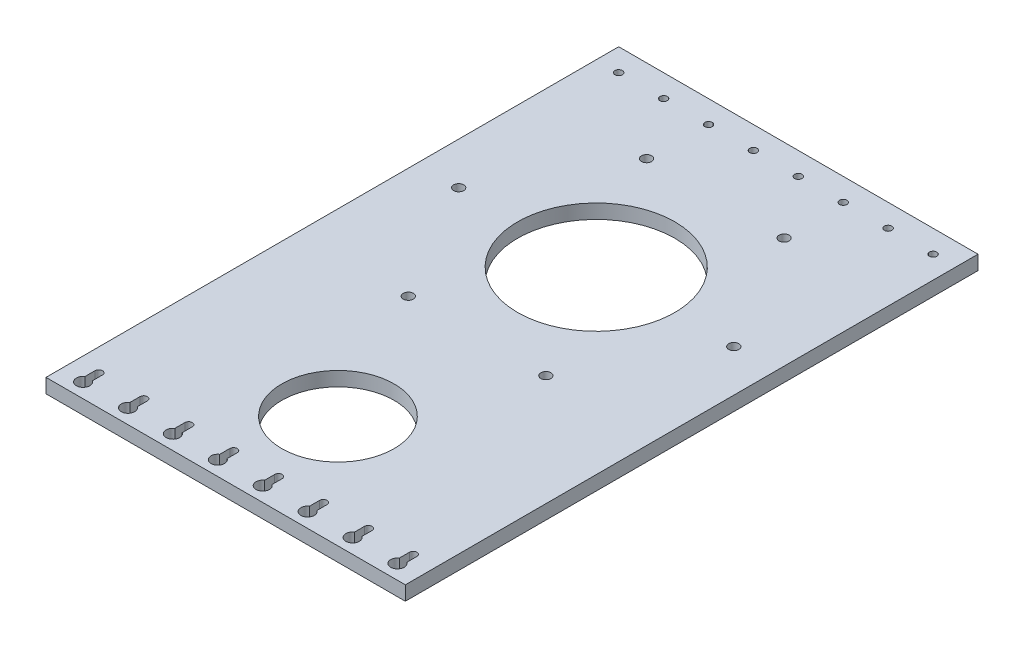
SolidWorks part; units mm, degrees
material "6061 Alloy"
ref_plane "Front Plane" through (0, 0, 0) normal (0, 0, 1) x (1, 0, 0)
ref_plane "Top Plane" through (0, 0, 0) normal (0, 1, 0) x (1, 0, 0)
ref_plane "Right Plane" through (0, 0, 0) normal (1, 0, 0) x (0, 0, -1)
sketch "Sketch1" plane through (0, 0, 0) normal (0, 1, 0) x (1, 0, 0)
  line L0 (80, 255) -> (80, 0) construction
  line L1 (0, 0) -> (160, 0)
  line L2 (0, 0) -> (0, 255)
  line L3 (0, 255) -> (160, 255)
  line L4 (160, 0) -> (160, 255)
  line L5 (80, 165) -> (141.25, 165) construction
  line L6 (10, 6.5) -> (10, 13.5) construction
  line L8 (14.5, 0) -> (14.5, 255) construction
  line L9 (14.5, 131) -> (0, 131) construction
  line L11 (0, 131) -> (0, 121) construction
  line L13 (8.35, 6.5) -> (8.35, 13.5)
  line L14 (11.65, 6.5) -> (11.65, 13.5)
  line L15 (10, 245) -> (10, 0) construction
  line L16 (31.65, 6.5) -> (31.65, 13.5)
  line L17 (28.35, 6.5) -> (28.35, 13.5)
  line L18 (30, 6.5) -> (30, 13.5) construction
  line L19 (51.65, 6.5) -> (51.65, 13.5)
  line L20 (48.35, 6.5) -> (48.35, 13.5)
  line L21 (50, 6.5) -> (50, 13.5) construction
  line L22 (71.65, 6.5) -> (71.65, 13.5)
  line L23 (68.35, 6.5) -> (68.35, 13.5)
  line L24 (70, 6.5) -> (70, 13.5) construction
  line L25 (91.65, 6.5) -> (91.65, 13.5)
  line L26 (88.35, 6.5) -> (88.35, 13.5)
  line L27 (90, 6.5) -> (90, 13.5) construction
  line L28 (111.65, 6.5) -> (111.65, 13.5)
  line L29 (108.35, 6.5) -> (108.35, 13.5)
  line L30 (110, 6.5) -> (110, 13.5) construction
  line L31 (131.65, 6.5) -> (131.65, 13.5)
  line L32 (128.35, 6.5) -> (128.35, 13.5)
  line L33 (130, 6.5) -> (130, 13.5) construction
  line L34 (151.65, 6.5) -> (151.65, 13.5)
  line L35 (148.35, 6.5) -> (148.35, 13.5)
  line L36 (150, 6.5) -> (150, 13.5) construction
  line L37 (10, 245) -> (30, 245) construction
  circle A0 centre (80, 165) radius 35
  circle A1 centre (80, 50) radius 25
  circle A2 centre (80, 165) radius 61.25 construction
  circle A3 centre (141.25, 165) radius 2.25
  circle A4 centre (110.625, 111.9559) radius 2.25
  circle A5 centre (49.375, 111.9559) radius 2.25
  circle A6 centre (18.75, 165) radius 2.25
  circle A7 centre (49.375, 218.0441) radius 2.25
  circle A8 centre (110.625, 218.0441) radius 2.25
  circle A12 centre (80, 165) radius 78 construction
  circle A13 centre (10, 245) radius 1.65
  arc A14 (8.35, 6.5) -> (11.65, 6.5) centre (10, 6.5) ccw
  arc A15 (11.65, 13.5) -> (8.35, 13.5) centre (10, 13.5) ccw
  circle A16 centre (30, 245) radius 1.65
  arc A17 (28.35, 6.5) -> (31.65, 6.5) centre (30, 6.5) ccw
  arc A18 (31.65, 13.5) -> (28.35, 13.5) centre (30, 13.5) ccw
  circle A19 centre (50, 245) radius 1.65
  arc A20 (48.35, 6.5) -> (51.65, 6.5) centre (50, 6.5) ccw
  arc A21 (51.65, 13.5) -> (48.35, 13.5) centre (50, 13.5) ccw
  circle A22 centre (70, 245) radius 1.65
  arc A23 (68.35, 6.5) -> (71.65, 6.5) centre (70, 6.5) ccw
  arc A24 (71.65, 13.5) -> (68.35, 13.5) centre (70, 13.5) ccw
  circle A25 centre (90, 245) radius 1.65
  arc A26 (88.35, 6.5) -> (91.65, 6.5) centre (90, 6.5) ccw
  arc A27 (91.65, 13.5) -> (88.35, 13.5) centre (90, 13.5) ccw
  circle A28 centre (110, 245) radius 1.65
  arc A29 (108.35, 6.5) -> (111.65, 6.5) centre (110, 6.5) ccw
  arc A30 (111.65, 13.5) -> (108.35, 13.5) centre (110, 13.5) ccw
  circle A31 centre (130, 245) radius 1.65
  arc A32 (128.35, 6.5) -> (131.65, 6.5) centre (130, 6.5) ccw
  arc A33 (131.65, 13.5) -> (128.35, 13.5) centre (130, 13.5) ccw
  circle A34 centre (150, 245) radius 1.65
  arc A35 (148.35, 6.5) -> (151.65, 6.5) centre (150, 6.5) ccw
  arc A36 (151.65, 13.5) -> (148.35, 13.5) centre (150, 13.5) ccw
  point P15 (80, 165)
  point P29 (10, 10)
  point P30 (0, 0)
  point P31 (0, 0)
  point P32 (0, 0)
  point P33 (0, 0)
  point P55 (30, 10)
  point P65 (50, 10)
  point P74 (70, 10)
  point P83 (90, 10)
  point P92 (110, 10)
  point P101 (130, 10)
  point P110 (150, 10)
  dimension "D3" = 70
  dimension "D4" = 50
  dimension "D7" = 122.5
  dimension "D8" = 4.5
  dimension "D11" = 124
  dimension "D16" = 156
  dimension "D19" = 3.3
  dimension "D24" = 235
  dimension "D1" = 160
  dimension "D2" = 255
  dimension "D5" = 115
  dimension "D6" = 90
  dimension "D10" = 61.25
  dimension "D12" = 65.5
  dimension "D18" = 80
  dimension "D20" = 10
  dimension "D21" = 10
  dimension "D22" = 3.3
  dimension "D23" = 7
  dimension "D26" = 20
  dimension "D25" = 8
  dimension "D9" = 6
extrude "Boss-Extrude1" add sketch "Sketch1" along normal blind 6.35 contours A1 | A0 | A4 | A8 | A7 | A6 | L4 L3 L2 L1 | A3 | A5 | A28 | A25 | A31 | A34 | A22 | A19 | A16 | A13 | L14 A15 L13 A14 | L16 A18 L17 A17 | L19 A21 L20 A20 | L22 A24 L23 A23 | L25 A27 L26 A26 | L28 A30 L29 A29 | L31 A33 L32 A32 | L34 A36 L35 A35 region at (80, 0, -165) region at (80, 0, -50) region at (110.625, 0, -111.9559) region at (18.75, 0, -165) region at (49.375, 0, -218.0441) region at (110.625, 0, -218.0441)
sketch "Sketch2" plane through (0, 6.35, 0) normal (0, 1, 0) x (1, 0, 0)
  line L0 (150, 6.5) -> (130, 6.5) construction
  circle A0 centre (150, 6.5) radius 3
  circle A1 centre (130, 6.5) radius 3
  circle A2 centre (110, 6.5) radius 3
  circle A3 centre (90, 6.5) radius 3
  circle A4 centre (70, 6.5) radius 3
  circle A5 centre (50, 6.5) radius 3
  circle A6 centre (30, 6.5) radius 3
  circle A7 centre (10, 6.5) radius 3
  dimension "D1" = 6
  dimension "D2" = 20
extrude "Cut-Extrude1" cut sketch "Sketch2" against normal up to next
